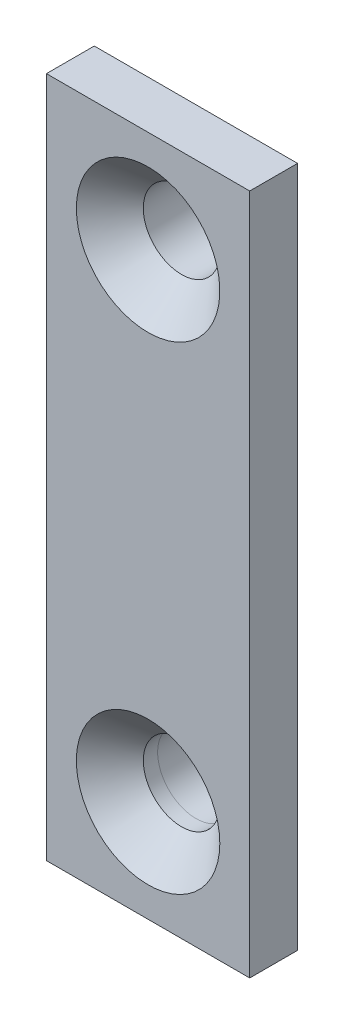
SolidWorks part; units mm, degrees
ref_plane "Front Plane" through (0, 0, 0) normal (1, 0, 0) x (0, 1, 0)
ref_plane "Top Plane" through (0, 0, 0) normal (0, 0, 1) x (0, 1, 0)
ref_plane "Right Plane" through (0, 0, 0) normal (0, 1, 0) x (-1, 0, 0)
sketch "Sketch1" plane through (0, 0, 0) normal (0, 0, 1) x (0, 1, 0)
  line L0 (0, 2.25) -> (0, -2.25) construction
  line L1 (-12.25, 2.25) -> (12.25, 2.25)
  line L2 (-12.25, 2.25) -> (-12.25, -2.25)
  line L3 (-12.25, -2.25) -> (12.25, -2.25)
  line L4 (12.25, 2.25) -> (12.25, -2.25)
  line L5 (-10, 0) -> (10, 0) construction
  line L6 (-14.25, 4.25) -> (-14.25, -4.25)
  line L7 (-14.25, -4.25) -> (14.25, -4.25)
  line L8 (14.25, 4.25) -> (14.25, -4.25)
  line L9 (-14.25, 4.25) -> (14.25, 4.25)
  line L10 (-7.5, 2.25) -> (-7.5, -2.25)
  line L11 (7.5, 2.25) -> (7.5, -2.25)
  circle A0 centre (-10, 0) radius 1.6
  circle A1 centre (10, 0) radius 1.6
  point P8 (0, 0)
  dimension "D3" = 3.2
  dimension "D4" = 3.2
  dimension "D1" = 4.5
  dimension "D2" = 24.5
  dimension "D5" = 20
  dimension "D7" = 2.5
  dimension "D8" = 2.5
  dimension "D6" = 2
extrude "Boss-Extrude1" add sketch "Sketch1" along normal blind 2 contours L4 L1 L2 L3 A1 A0 | L10 L1 L2 L3 A0 region at (-2.1846, -9.875, 0) region at (-2.1846, 9.875, 0)
extrude "Boss-Extrude2" add sketch "Sketch1<3>" along normal blind 2 from surface contours L9 L6 L7 L8 L1 L4 L3 L2 | L4 L1 L2 L3 A1 A0 | L11 L1 L10 L3 | L10 L1 L2 L3 A0 region at (-2.1846, -9.875, 0) region at (0, 0, 0) region at (-2.1846, 9.875, 0) region at (-3.9526, 0, 0) starting at face at (1.6, 10, 2)
sketch "Sketch1<3>" plane through (0, 0, 0) normal (0, 0, 1) x (0, 1, 0) same geometry as "Sketch1"
chamfer "Chamfer1" distance 1.4 angle 45 2 edges at (1.6, 10, 4) (1.6, -10, 4)
